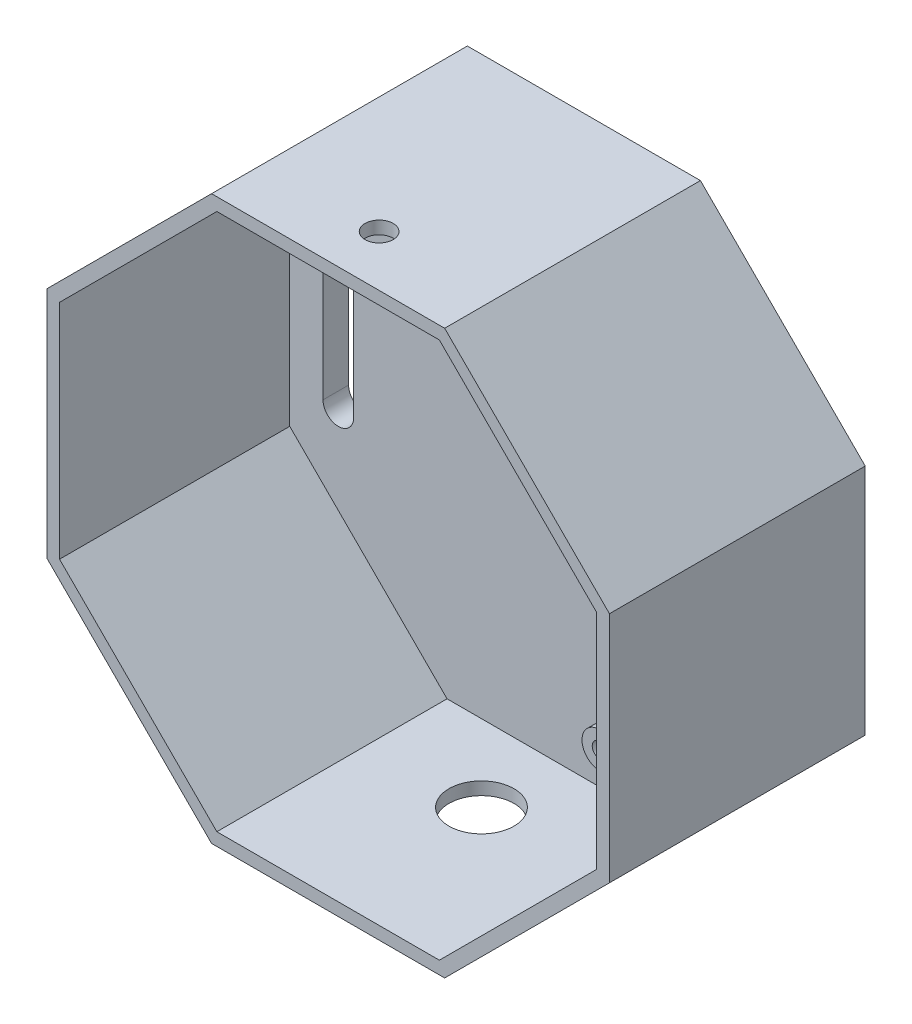
SolidWorks part; units mm, degrees
material "ABS PC"
ref_plane "Front Plane" through (0, 0, 0) normal (0, 0, 1) x (1, 0, 0)
ref_plane "Top Plane" through (0, 0, 0) normal (0, 1, 0) x (1, 0, 0)
ref_plane "Right Plane" through (0, 0, 0) normal (1, 0, 0) x (0, 0, -1)
sketch "Sketch8" plane through (0, 0, 0) normal (0, 0, 1) x (1, 0, 0)
  line L1 (55, 22.7817) -> (22.7817, 55)
  line L2 (22.7817, 55) -> (-22.7817, 55)
  line L3 (-22.7817, 55) -> (-55, 22.7817)
  line L4 (-55, 22.7817) -> (-55, -22.7817)
  line L5 (-55, -22.7817) -> (-22.7817, -55)
  line L6 (-22.7817, -55) -> (22.7817, -55)
  line L7 (22.7817, -55) -> (55, -22.7817)
  line L8 (55, -22.7817) -> (55, 22.7817)
  circle A0 centre (0, 0) radius 55 construction
extrude "Boss-Extrude3" add sketch "Sketch8" along normal blind 50
sketch "Sketch9" plane through (0, 0, 50) normal (0, 0, 1) x (1, 0, 0)
  line L1 (52.5, 21.7462) -> (21.7462, 52.5)
  line L2 (21.7462, 52.5) -> (-21.7462, 52.5)
  line L3 (-21.7462, 52.5) -> (-52.5, 21.7462)
  line L4 (-52.5, 21.7462) -> (-52.5, -21.7462)
  line L5 (-52.5, -21.7462) -> (-21.7462, -52.5)
  line L6 (-21.7462, -52.5) -> (21.7462, -52.5)
  line L7 (21.7462, -52.5) -> (52.5, -21.7462)
  line L8 (52.5, -21.7462) -> (52.5, 21.7462)
  circle A0 centre (0, 0) radius 52.5 construction
extrude "Cut-Extrude3" cut sketch "Sketch9" against normal blind 45
hole_wizard "Antenna Hole" positions "Sketch10" profile "Sketch12" legacy end condition through all
sketch "Sketch10" plane through (0, -52.5, 0) normal (0, 1, 0) x (1, 0, 0)
  point P0 (0, -20.0175)
sketch "Sketch12" plane through (0, -52.5, 20.0175) normal (1, 0, 0) x (0, 0, 1)
  line L0 (0, 0) -> (0, 2.5)
  line L1 (0, 2.5) -> (6.35, 2.5)
  line L2 (6.35, 2.5) -> (6.35, 0)
  line L3 (6.35, 0) -> (0, 0)
  line L4 (0, 110) -> (0, -10) construction
  dimension "Diameter" = 12.7
  dimension "Depth" = 2.5
sketch "Sketch15" plane through (0, 0, 0) normal (0, 0, -1) x (-1, 0, 0)
  line L0 (-43, 13.2597) -> (-43, -13.2907) construction
  line L1 (-40, 13.2597) -> (-40, -13.2907)
  line L2 (-46, 13.2597) -> (-46, -13.2907)
  line L3 (-52.5, -21.7462) -> (-52.5, 21.7462) construction
  arc A0 (-40, 13.2597) -> (-46, 13.2597) centre (-43, 13.2597) ccw
  arc A1 (-46, -13.2907) -> (-40, -13.2907) centre (-43, -13.2907) ccw
  point P2 (-43, -0.0155)
  point P7 (-46, -0.0155)
  dimension "D1" = 6.5
extrude "Right GPIO Slot" cut sketch "Sketch15" against normal blind 5 and the other way through all
sketch "Sketch18" plane through (0, 0, 0) normal (0, 0, -1) x (-1, 0, 0)
  line L0 (43, 12.9852) -> (43, -14.0148) construction
  line L1 (46, 12.9852) -> (46, -14.0148)
  line L2 (40, 12.9852) -> (40, -14.0148)
  line L3 (52.5, 21.7462) -> (52.5, -21.7462) construction
  arc A0 (46, 12.9852) -> (40, 12.9852) centre (43, 12.9852) ccw
  arc A1 (40, -14.0148) -> (46, -14.0148) centre (43, -14.0148) ccw
  point P2 (43, -0.5148)
  point P10 (46, -0.5148)
  dimension "D1" = 6.5
extrude "Left GPIO Slot" cut sketch "Sketch18" against normal blind 5
hole_wizard "PV Panel Barrel Jack Hole" positions "Sketch19" profile "Sketch21" legacy end condition up to next
sketch "Sketch19" plane through (0, 55, 0) normal (0, 1, 0) x (1, 0, 0)
  point P0 (0, -40.0311)
  point P3 (0, -40.0311)
sketch "Sketch21" plane through (0, 55, 40.0311) normal (1, 0, 0) x (0, 0, 1)
  line L0 (0, 0) -> (0, 110)
  line L1 (0, 110) -> (2.75, 110)
  line L2 (2.75, 110) -> (2.75, 0)
  line L3 (2.75, 0) -> (0, 0)
  line L4 (0, 110) -> (0, -10) construction
  dimension "Diameter" = 5.5
  dimension "Depth" = 110
sketch "Sketch22" plane through (0, 0, 0) normal (0, 0, -1) x (-1, 0, 0)
  circle A0 centre (15.2748, 17.4515) radius 3.5
extrude "Mounting Hole 1" add sketch "Sketch22" against normal blind 10
sketch "Sketch23" plane through (0, 0, 0) normal (0, 0, -1) x (-1, 0, 0)
  circle A0 centre (-13.1313, -41.2706) radius 3.5
extrude "Mounting Hole 2" add sketch "Sketch23" against normal blind 10
hole_wizard "Mounting Holes" positions "Sketch26" profile "Sketch27" legacy
sketch "Sketch26" plane through (0, 0, 10) normal (0, 0, 1) x (1, 0, 0)
  point P0 (13.1313, -41.2706)
  point P3 (-15.2748, 17.4515)
sketch "Sketch27" plane through (13.1313, -41.2706, 10) normal (1, 0, 0) x (0, -1, 0)
  line L0 (0, 0) -> (0, 4.999)
  line L1 (0, 4.999) -> (1.5, 4.999)
  line L2 (1.5, 4.999) -> (1.5, 0)
  line L3 (1.5, 0) -> (0, 0)
  line L4 (0, 110) -> (0, -10) construction
  dimension "Diameter" = 3
  dimension "Depth" = 4.999
